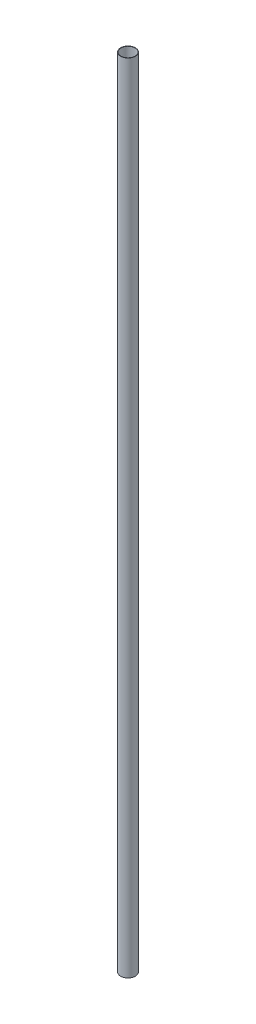
SolidWorks part; units mm, degrees
material "1060 Alloy"
ref_plane "Front Plane" through (0, 0, 0) normal (0, 0, 1) x (1, 0, 0)
ref_plane "Top Plane" through (0, 0, 0) normal (0, 1, 0) x (1, 0, 0)
ref_plane "Right Plane" through (0, 0, 0) normal (1, 0, 0) x (0, 0, -1)
sketch "Sketch1" plane through (0, 0, 0) normal (0, 1, 0) x (1, 0, 0)
  circle A0 centre (-79.1203, 11.8931) radius 12
  circle A1 centre (-79.1203, 11.8931) radius 12.5
  dimension "D1" = 24
  dimension "D2" = 25
extrude "Boss-Extrude1" add sketch "Sketch1" along normal blind 1350
